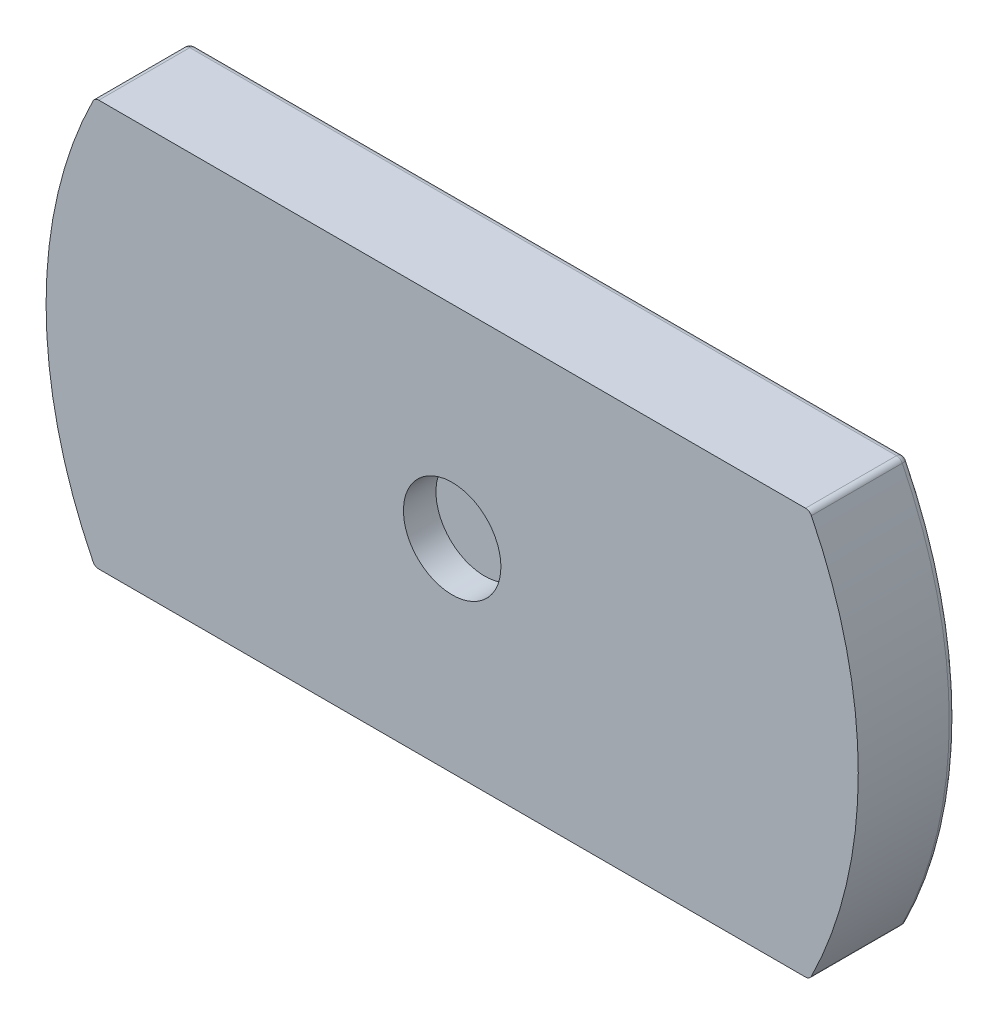
SolidWorks part; units mm, degrees
ref_plane "Front Plane" through (0, 0, 0) normal (0, 0, 1) x (1, 0, 0)
ref_plane "Top Plane" through (0, 0, 0) normal (0, 1, 0) x (1, 0, 0)
ref_plane "Right Plane" through (0, 0, 0) normal (1, 0, 0) x (0, 0, -1)
sketch "Sketch1" plane through (0, 0, 0) normal (0, 0, 1) x (1, 0, 0)
  line L1 (317.5, 76.2) -> (-317.5, 76.2)
  line L2 (317.5, 76.2) -> (317.5, 393.7)
  line L3 (317.5, 393.7) -> (-317.5, 393.7)
  line L4 (-317.5, 76.2) -> (-317.5, 393.7)
  line L5 (317.5, 76.2) -> (-317.5, 393.7) construction
  line L6 (317.5, 393.7) -> (-317.5, 76.2) construction
  point P0 (0, 234.95)
  dimension "D1" = 76.2
  dimension "D2" = 635
  dimension "D3" = 317.5
extrude "Boss-Extrude2" add sketch "Sketch1" along normal blind 76.2
sketch "Sketch3" plane through (0, 0, 76.2) normal (0, 0, 1) x (1, 0, 0)
  line L0 (0, 393.7) -> (0, 0) construction
  line L1 (317.5, 393.7) -> (-317.5, 393.7) construction
  line L2 (-279.4, 393.7) -> (-279.4, 76.2) construction
  line L3 (-317.5, 76.2) -> (317.5, 76.2) construction
  line L4 (-317.5, 393.7) -> (-317.5, 76.2) construction
  line L5 (-279.4, 393.7) -> (279.4, 393.7)
  line L6 (-279.4, 76.2) -> (279.4, 76.2)
  arc A0 (-279.4, 393.7) -> (-279.4, 76.2) centre (32.2792, 234.95) ccw
  arc A1 (279.4, 393.7) -> (279.4, 76.2) centre (-32.2792, 234.95) cw
  dimension "D1" = 38.1
extrude "Cut-Extrude1" cut sketch "Sketch3" against normal blind 137.16 flip side to cut
fillet "Fillet1" radius 5.08 8 edges at (279.4, 393.7, 38.1) (-279.4, 393.7, 38.1) (-279.4, 76.2, 38.1) (279.4, 76.2, 38.1) (-317.5, 234.95, 0) (0, 393.7, 0) (317.5, 234.95, 0) (0, 76.2, 0)
sketch "Sketch5" plane through (0, 0, 0) normal (0, 0, -1) x (-1, 0, 0)
  line L0 (-260.1226, 106.68) -> (-260.1226, 363.22) construction
  line L8 (-260.1226, 106.68) -> (260.1226, 106.68)
  line L9 (260.1226, 363.22) -> (-260.1226, 363.22)
  line L10 (-260.1226, 106.68) -> (260.1226, 106.68) construction
  line L11 (260.1226, 363.22) -> (-260.1226, 363.22) construction
  circle A4 centre (-260.1226, 106.68) radius 6.35
  arc A6 (260.1226, 106.68) -> (260.1226, 363.22) centre (-32.2792, 234.95) ccw
  arc A7 (-260.1226, 363.22) -> (-260.1226, 106.68) centre (32.2792, 234.95) ccw
  arc A8 (260.1226, 106.68) -> (260.1226, 363.22) centre (-32.2792, 234.95) ccw construction
  arc A9 (-260.1226, 363.22) -> (-260.1226, 106.68) centre (32.2792, 234.95) ccw construction
  dimension "D2" = 12.7
  dimension "D1" = 25.4
extrude "Cut-Extrude2" cut sketch "Sketch5" against normal blind 20.32
pattern_linear "LPattern1" count 18 spacing 30.48 along (-1, 0, 0) of "Cut-Extrude2"
sketch "Sketch6" plane through (0, 0, 0) normal (0, 0, -1) x (-1, 0, 0)
  line L0 (-260.1226, 106.68) -> (-260.1226, 363.22) construction
pattern_linear "LPattern2" count 9 spacing 31.75 along (0, 1, 0) of "Cut-Extrude2", "LPattern1"
pattern_circular "CirPattern1" count 6 every 8 about axis through (-32.2792, 234.95, -60.96) along (0, 0, 1) of "Cut-Extrude2"
mirror "Mirror1" about plane through (0, 0, 0) normal (1, 0, 0) of "CirPattern1"
sketch "Sketch8" plane through (0, 0, 76.2) normal (0, 0, 1) x (1, 0, 0)
  line L0 (-317.5, 234.95) -> (317.5, 234.95) construction
  line L1 (0, 393.7) -> (0, 76.2) construction
  line L2 (276.2707, 393.7) -> (-276.2707, 393.7) construction
  line L3 (-276.2707, 76.2) -> (276.2707, 76.2) construction
  circle A0 centre (0, 234.95) radius 38.1
  arc A1 (-280.818, 390.8847) -> (-280.818, 79.0153) centre (32.2792, 234.95) ccw construction
  arc A2 (280.818, 79.0153) -> (280.818, 390.8847) centre (-32.2792, 234.95) ccw construction
  dimension "D1" = 76.2
  dimension "D2" = 0
extrude "Cut-Extrude3" cut sketch "Sketch8" against normal blind 25.4
